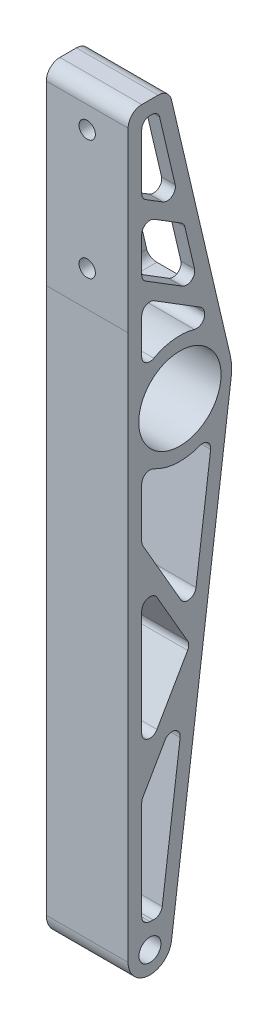
SolidWorks part; units mm, degrees
material "6061-T6 (SS)"
ref_plane "Front Plane" through (0, 0, 0) normal (0, 0, 1) x (1, 0, 0)
ref_plane "Top Plane" through (0, 0, 0) normal (0, 1, 0) x (1, 0, 0)
ref_plane "Right Plane" through (0, 0, 0) normal (1, 0, 0) x (0, 0, -1)
sketch "Sketch1" plane through (0, 0, 0) normal (1, 0, 0) x (0, 0, -1)
  line L0 (-8, 0) -> (-8, 270)
  line L1 (11, 169.6437) -> (0, 0) construction
  line L2 (7.933, -1.0331) -> (29.8409, 167.1901)
  line L3 (-8, 270) -> (7, 270)
  line L4 (7, 270) -> (29.499, 173.9783)
  circle A0 centre (0, 0) radius 4.05
  arc A1 (-8, 0) -> (7.933, -1.0331) centre (0, 0) ccw
  arc A2 (29.8409, 167.1901) -> (29.499, 173.9783) centre (11, 169.6437) ccw
  circle A3 centre (11, 169.6437) radius 15.1
  dimension "D1" = 8.1
  dimension "D2" = 16
  dimension "D4" = 38
  dimension "D6" = 30.2
  dimension "D3" = 270
  dimension "D5" = 170
  dimension "D7" = 15
extrude "Boss-Extrude1" add sketch "Sketch1" along normal blind 15 and the other way blind 15
sketch "Sketch3" plane through (0, 0, 8) normal (0, 0, 1) x (1, 0, 0)
  line L0 (15, 270) -> (15, 0) construction
  line L1 (-15, 270) -> (15, 270)
  line L2 (-15, 270) -> (-15, 200)
  line L3 (-15, 200) -> (15, 200)
  line L4 (15, 270) -> (15, 200)
  dimension "D1" = 70
split line "Split Line1"
sketch "Sketch5" plane through (0, 0, 0) normal (1, 0, 0) x (0, 0, -1)
  line L1 (-3, 265) -> (63.8342, 265)
  line L2 (-3, 265) -> (-3, 195.1437)
  line L3 (-3, 195.1437) -> (63.8342, 195.1437)
  line L4 (63.8342, 265) -> (63.8342, 195.1437)
  line L5 (-8, 270) -> (-8, 200) construction
  line L6 (7, 270) -> (-8, 270) construction
  circle A0 centre (11, 169.6437) radius 15.1 construction
  dimension "D1" = 5
  dimension "D2" = 25.5
  dimension "D3" = 5
extrude "Cut-Extrude2" cut sketch "Sketch5" against normal blind 10 and the other way blind 10
sketch "Sketch4" plane through (15, 0, 0) normal (1, 0, 0) x (0, 0, -1)
  line L0 (-3, 155.3609) -> (-3, 8.4853)
  line L1 (-8, 200) -> (-8, 0) construction
  line L2 (23.0383, 153.6725) -> (4.0707, 8.0268)
  line L3 (7.933, -1.0331) -> (29.8409, 167.1901) construction
  line L4 (-3, 183.9266) -> (-3, 265)
  line L5 (-3, 265) -> (3.0361, 265)
  line L6 (3.0361, 265) -> (21.3724, 186.7438)
  line L7 (-3, 240) -> (10.9167, 231.3669)
  line L8 (29.499, 173.9783) -> (7, 270) construction
  line L9 (7, 270) -> (-8, 270) construction
  line L10 (-3, 130.3609) -> (15.7688, 97.8524)
  line L11 (-3, 120.3609) -> (14.7061, 89.6929)
  line L12 (-3, 234.1161) -> (12.5299, 224.4823)
  line L13 (-3, 214.1161) -> (18.0131, 201.0809)
  line L14 (14.7061, 89.6929) -> (-3, 59.025)
  line L15 (13.0245, 76.7803) -> (-3, 49.025)
  line L16 (-3, 208.2322) -> (19.6262, 194.1963)
  circle A0 centre (0, 0) radius 9
  circle A1 centre (11, 169.6437) radius 20
  dimension "D1" = 40
  dimension "D2" = 18
  dimension "D3" = 5
  dimension "D4" = 5
  dimension "D5" = 5
  dimension "D6" = 5
  dimension "D7" = 5
  dimension "D8" = 45
  dimension "D9" = 25
  dimension "D10" = 25
  dimension "D11" = 30
  dimension "D12" = 30
  dimension "D13" = 5
  dimension "D14" = 5
  dimension "D15" = 45
  dimension "D16" = 20
  dimension "D17" = 5
extrude "Cut-Extrude1" cut sketch "Sketch4" against normal through all both and the other way through all contours A1 L0 L10 L2 | A0 L2 L11 L0 | A1 L6 L4 | L4 L6 L5 | L14 L11 L0 | L4 L13 L6 L12 region at (15, 131.8968, -9.8249) region at (15, 195.1997, -6.0352) region at (15, 89.6929, -2.902) region at (15, 217.9062, -6.2043) region at (15, 39.0713, -3.3723) region at (15, 248.5264, -2.3803)
fillet "Fillet1" radius 3 35 edges at (0, 186.7438, -21.3724) (0, 183.9266, 3) (0, 194.1963, -19.6262) (-12.5, 208.2322, 3) (12.5, 224.4823, -12.5299) (-12.5, 224.4823, -12.5299) (12.5, 201.0809, -18.0131) (-12.5, 214.1161, 3) (12.5, 214.1161, 3) (12.5, 208.2322, 3) (-12.5, 234.1161, 3) (12.5, 234.1161, 3) (12.5, 231.3669, -10.9167) (-12.5, 231.3669, -10.9167) (12.5, 265, -3.0361) (-12.5, 265, -3.0361) (-12.5, 240, 3) (12.5, 240, 3) (0, 265, 3) (0, 8.0268, -4.0707) (0, 8.4853, 3) (0, 49.025, 3) (0, 76.7803, -13.0245) (0, 59.025, 3) (0, 89.6929, -14.7061) (0, 120.3609, 3) (0, 97.8524, -15.7688) (0, 130.3609, 3) (0, 153.6725, -23.0383) (0, 155.3609, 3) (-12.5, 201.0809, -18.0131) (-10, 265, -5.6038) (10, 265, -5.6038) (-10, 195.1437, -21.3193) (10, 195.1437, -21.3193)
fillet "Fillet2" radius 5 2 edges at (0, 270, 8) (0, 270, -7)
sketch "Sketch6" plane through (0, 0, 8) normal (0, 0, 1) x (1, 0, 0)
  circle A0 centre (0, 257) radius 3
  circle A1 centre (0, 213) radius 3
extrude "Cut-Extrude3" cut sketch "Sketch6" against normal blind 5
